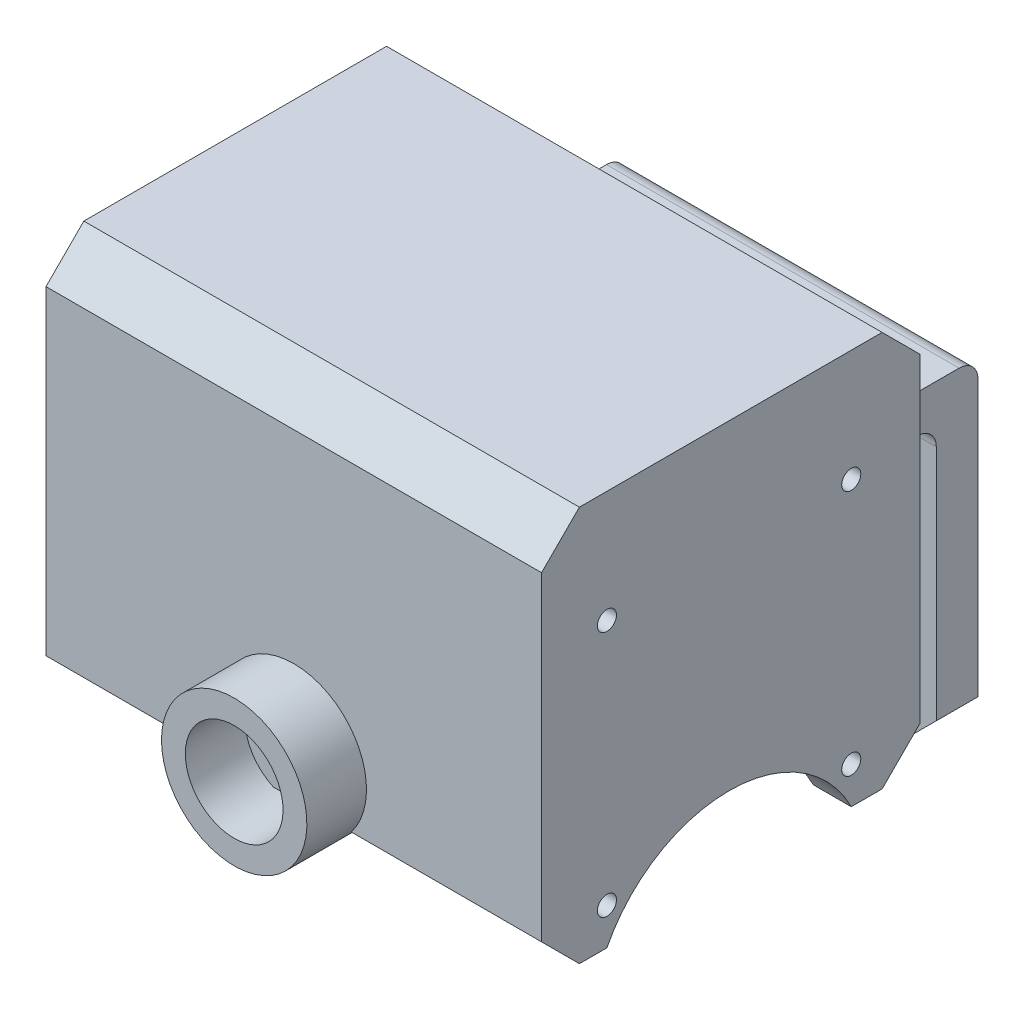
SolidWorks part; units mm, degrees
material "PLA"
ref_plane "Front Plane" through (0, 0, 0) normal (0, 0, 1) x (1, 0, 0)
ref_plane "Top Plane" through (0, 0, 0) normal (0, 1, 0) x (1, 0, 0)
ref_plane "Right Plane" through (0, 0, 0) normal (1, 0, 0) x (0, 0, -1)
sketch "Sketch1" plane through (0, 0, 0) normal (1, 0, 0) x (0, 0, -1)
  line L1 (0, 0) -> (25, 0)
  line L2 (0, 0) -> (0, 30)
  line L3 (0, 30) -> (25, 30)
  line L4 (25, 0) -> (25, 30)
  dimension "D1" = 30
  dimension "D2" = 25
extrude "Boss-Extrude1" add sketch "Sketch1" along normal blind 3.175
sketch "Sketch2" plane through (0, 0, 0) normal (-1, 0, 0) x (0, 0, 1)
  line L1 (-25, 30) -> (0, 30)
  line L2 (-25, 30) -> (-25, 33.175)
  line L3 (-25, 33.175) -> (0, 33.175)
  line L4 (0, 30) -> (0, 33.175)
  dimension "D1" = 3.175
extrude "Boss-Extrude2" add sketch "Sketch2" against normal blind 41.58
sketch "Sketch3" plane through (0, 30, 0) normal (0, -1, 0) x (1, 0, 0)
  line L0 (41.58, 0) -> (3.175, 0) construction
  line L1 (41.58, -25) -> (38.405, -25)
  line L2 (41.58, -25) -> (41.58, 0)
  line L3 (41.58, 0) -> (38.405, 0)
  line L4 (38.405, -25) -> (38.405, 0)
  dimension "D1" = 3.175
extrude "Boss-Extrude3" add sketch "Sketch3" along normal up to surface (30 mm away) up to face at (1.5875, 0, -12.5)
sketch "Sketch4" plane through (0, 0, 0) normal (-1, 0, 0) x (0, 0, 1)
  circle A0 centre (-12.36, -5.21) radius 11.5
  dimension "D1" = 23
extrude "Cut-Extrude1" cut sketch "Sketch4" against normal up to next
sketch "Sketch5" plane through (0, 0, 0) normal (-1, 0, 0) x (0, 0, 1)
  circle A0 centre (-22.61, 3.09) radius 0.8
  circle A1 centre (-22.61, 23.79) radius 0.8
  circle A2 centre (-2.11, 23.79) radius 0.8
  circle A3 centre (-2.11, 3.09) radius 0.8
extrude "Cut-Extrude2" cut sketch "Sketch5" against normal up to next
sketch "Sketch6" plane through (41.58, 0, 0) normal (1, 0, 0) x (0, 0, -1)
  line L1 (1.76, 5.74) -> (22.96, 5.74)
  line L2 (1.76, 5.74) -> (1.76, 12.115)
  line L3 (1.76, 12.115) -> (22.96, 12.115)
  line L4 (22.96, 5.74) -> (22.96, 12.115)
  circle A0 centre (2.11, 3.09) radius 0.8
  circle A1 centre (22.61, 3.09) radius 0.8
  circle A2 centre (22.61, 27.54) radius 0.7999
  circle A3 centre (2.11, 27.54) radius 0.8
extrude "Cut-Extrude3" cut sketch "Sketch6" against normal up to next
sketch "Sketch7" plane through (41.58, 0, 0) normal (1, 0, 0) x (0, 0, -1)
  circle A0 centre (12.36, -5.21) radius 11.5
  dimension "D1" = 23
extrude "Cut-Extrude4" cut sketch "Sketch7" against normal up to next
sketch "Sketch8" plane through (0, 0, 0) normal (0, 0, 1) x (1, 0, 0)
  line L8 (0, 33.175) -> (0, 0)
  line L9 (0, 0) -> (3.175, 0)
  line L10 (3.175, 0) -> (3.175, 30)
  line L11 (3.175, 30) -> (38.405, 30)
  line L12 (38.405, 30) -> (38.405, 0)
  line L13 (38.405, 0) -> (41.58, 0)
  line L14 (41.58, 0) -> (41.58, 33.175)
  line L15 (41.58, 33.175) -> (0, 33.175)
  line L16 (0, 33.175) -> (0, 0)
  line L17 (0, 0) -> (3.175, 0)
  line L18 (3.175, 0) -> (3.175, 30)
  line L19 (3.175, 30) -> (38.405, 30)
  line L20 (38.405, 30) -> (38.405, 0)
  line L21 (38.405, 0) -> (41.58, 0)
  line L22 (41.58, 0) -> (41.58, 33.175)
  line L23 (41.58, 33.175) -> (0, 33.175)
  dimension "D1" = 0
extrude "Boss-Extrude4" add sketch "Sketch8" along normal blind 0.2
sketch "Sketch9" plane through (0, 0, 0.2) normal (0, 0, 1) x (1, 0, 0)
  line L1 (0, 0) -> (41.58, 0)
  line L2 (0, 0) -> (0, 33.175)
  line L3 (0, 33.175) -> (41.58, 33.175)
  line L4 (41.58, 0) -> (41.58, 33.175)
extrude "Boss-Extrude5" add sketch "Sketch9" along normal blind 3.175
sketch "Sketch10" plane through (0, 0, -25) normal (0, 0, -1) x (-1, 0, 0)
  line L8 (0, 0) -> (0, 33.175)
  line L9 (0, 33.175) -> (-41.58, 33.175)
  line L10 (-41.58, 33.175) -> (-41.58, 0)
  line L11 (-41.58, 0) -> (-38.405, 0)
  line L12 (-38.405, 0) -> (-38.405, 30)
  line L13 (-38.405, 30) -> (-3.175, 30)
  line L14 (-3.175, 30) -> (-3.175, 0)
  line L15 (-3.175, 0) -> (0, 0)
  line L16 (0, 0) -> (0, 33.175)
  line L17 (0, 33.175) -> (-41.58, 33.175)
  line L18 (-41.58, 33.175) -> (-41.58, 0)
  line L19 (-41.58, 0) -> (-38.405, 0)
  line L20 (-38.405, 0) -> (-38.405, 30)
  line L21 (-38.405, 30) -> (-3.175, 30)
  line L22 (-3.175, 30) -> (-3.175, 0)
  line L23 (-3.175, 0) -> (0, 0)
  dimension "D1" = 0
extrude "Boss-Extrude6" add sketch "Sketch10" along normal blind 0.2
sketch "Sketch11" plane through (0, 0, -25.2) normal (0, 0, -1) x (-1, 0, 0)
  line L1 (-41.58, 0) -> (0, 0)
  line L2 (-41.58, 0) -> (-41.58, 33.175)
  line L3 (-41.58, 33.175) -> (0, 33.175)
  line L4 (0, 0) -> (0, 33.175)
extrude "Boss-Extrude7" add sketch "Sketch11" along normal blind 3.175
chamfer "Chamfer1" distance 3.175 angle 45 2 edges at (20.79, 33.175, 3.375) (20.79, 33.175, -28.375)
chamfer "Chamfer2" distance 3.175 angle 45 2 edges at (20.79, 0, 3.375) (20.79, 0, -28.375)
sketch "Sketch13" plane through (0, 0, -28.375) normal (0, 0, -1) x (-1, 0, 0)
  line L0 (0, 3.175) -> (0, 30) construction
  line L1 (-35.58, 18.175) -> (-6, 18.175)
  line L3 (-35.58, 21.35) -> (-6, 21.35)
  line L5 (-35.58, 21.35) -> (-35.58, 18.175)
  line L6 (-6, 21.35) -> (-6, 18.175)
  line L7 (-41.58, 30) -> (-41.58, 3.175) construction
  line L9 (-41.58, 3.175) -> (0, 3.175) construction
  dimension "D1" = 3.175
  dimension "D2" = 6
  dimension "D3" = 6
  dimension "D4" = 15
extrude "Boss-Extrude8" add sketch "Sketch13" along normal blind 7.695
sketch "Sketch14" plane through (0, 18.175, 0) normal (0, -1, 0) x (1, 0, 0)
  line L0 (35.58, -35.745) -> (35.58, -39.2524) construction
  line L1 (-0.7092, -39.245) -> (9.3147, -39.245) construction
  line L7 (6, -35.745) -> (6, -39.245)
  line L8 (6, -39.245) -> (35.58, -39.245)
  line L9 (35.58, -35.745) -> (35.58, -39.245)
  line L11 (35.58, -36.07) -> (6, -36.07) construction
  line L12 (6, -35.745) -> (35.58, -35.745)
  dimension "D1" = 3.5
  dimension "D2" = 3.175
  dimension "D3" = 3.5
extrude "Boss-Extrude9" add sketch "Sketch14" against normal up to surface and the other way blind 25 up to face at (20.79, 21.35, -32.2225)
chamfer "Chamfer3" distance 3.5 angle 45 2 edges at (35.58, -6.825, -37.495) (6, -6.825, -37.495)
fillet "Fillet1" radius 1.5875 2 edges at (20.79, 21.35, -39.245) (20.79, 18.175, -35.745)
fillet "Fillet2" radius 1.5875 1 edges at (20.79, 21.35, -28.375)
sketch "Sketch16" plane through (0, 0, -39.245) normal (0, 0, -1) x (-1, 0, 0)
  line L0 (-20.79, 19.7625) -> (-20.79, 6.9025) construction
  line L1 (-6, 19.7625) -> (-35.58, 19.7625) construction
  circle A0 centre (-20.79, 6.9025) radius 6.1
  dimension "D2" = 12.2
  dimension "D1" = 12.86
extrude "Cut-Extrude5" cut sketch "Sketch16" against normal up to next
sketch "Sketch20" plane through (0, 0, -35.745) normal (0, 0, 1) x (1, 0, 0)
  circle A0 centre (20.79, 6.9025) radius 6.1 construction
  circle A1 centre (20.79, 6.9025) radius 6.1 construction
  circle A2 centre (20.79, 6.9025) radius 4.1
  circle A3 centre (20.79, 6.9025) radius 8
  dimension "D1" = 8.2
  dimension "D2" = 16
extrude "Boss-Extrude11" add sketch "Sketch20" along normal blind 5
sketch "Sketch21" plane through (0, -6.825, 0) normal (0, -1, 0) x (1, 0, 0)
  line L0 (20.79, -30.745) -> (20.79, -35.745) construction
  line L1 (28.79, -30.745) -> (12.79, -30.745) construction
  line L2 (32.08, -35.745) -> (9.5, -35.745) construction
  circle A0 centre (20.79, -33.245) radius 1.025
  dimension "D1" = 2.05
extrude "Cut-Extrude6" cut sketch "Sketch21" against normal up to surface (25 mm away)
sketch "Sketch23" plane through (0, 0, 3.375) normal (0, 0, 1) x (1, 0, 0)
  circle A2 centre (20.79, 6.9025) radius 4.1
  circle A4 centre (20.79, 6.9025) radius 6.1
  dimension "D1" = 8.2
  dimension "D2" = 12.2
extrude "Boss-Extrude12" add sketch "Sketch23" against normal blind 1.2 and the other way blind 5
chamfer "Chamfer4" distance 1.5 angle 45 3 edges at (6, 20.5563, -28.375) (35.58, 20.5563, -28.375) (20.79, 18.175, -28.375)
ref_plane "Plane1" through (51.58, 0, 0) normal (1, 0, 0) x (0, 0, -1)
mirror "Mirror1" about plane through (51.58, 0, 0) normal (1, 0, 0) of bodies 118
delete or keep bodies "Body-Delete/Keep 1" type delete bodies bodies 118
